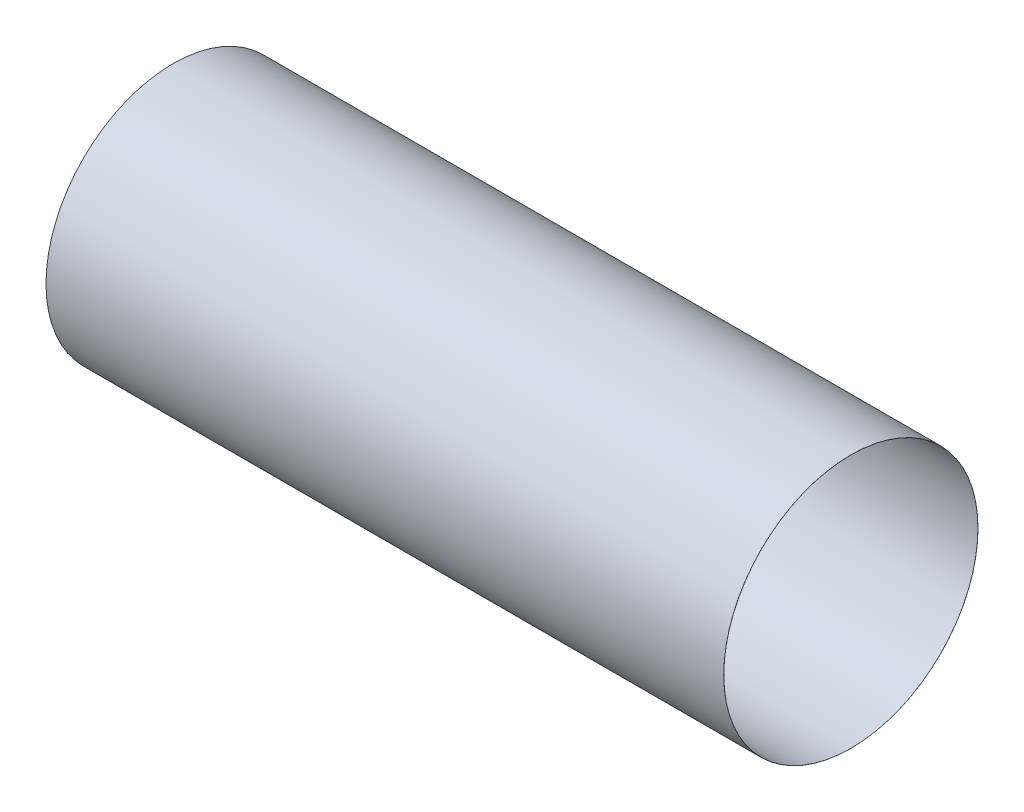
SolidWorks part; units mm, degrees
material "Air"
ref_plane "Front" through (0, 0, 0) normal (0, 0, 1) x (1, 0, 0)
ref_plane "Top" through (0, 0, 0) normal (0, 1, 0) x (1, 0, 0)
ref_plane "Right" through (0, 0, 0) normal (1, 0, 0) x (0, 0, -1)
sketch "Sketch2" plane through (0, 0, 0) normal (1, 0, 0) x (0, 0, -1)
  circle A0 centre (0, 0) radius 57.15
  dimension "D1" = 114.3
extrude "Extrude-Thin1" add sketch "Sketch2" along normal blind 304.8 thin thin type one direction wall 0.0254
